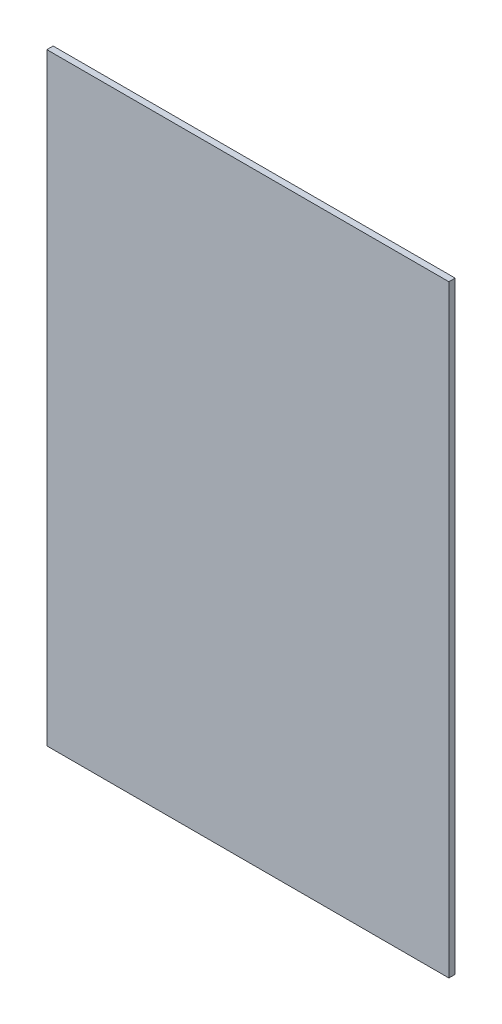
SolidWorks part; units mm, degrees
ref_plane "Front Plane" through (0, 0, 0) normal (0, 0, 1) x (1, 0, 0)
ref_plane "Top Plane" through (0, 0, 0) normal (0, 1, 0) x (1, 0, 0)
ref_plane "Right Plane" through (0, 0, 0) normal (1, 0, 0) x (0, 0, -1)
sketch "Sketch1" plane through (0, 0, 0) normal (0, 0, 1) x (1, 0, 0)
  line L0 (0, 0) -> (203.2, 0)
  line L1 (203.2, 0) -> (203.2, 304.8)
  line L2 (203.2, 304.8) -> (0, 304.8)
  line L3 (0, 304.8) -> (0, 0)
  dimension "D1" = 203.2
  dimension "D2" = 304.8
extrude "Boss-Extrude1" add sketch "Sketch1" along normal blind 3.175
equation "\"wall_thickness\" = 0.125in"
equation "\"base_thickness\" = 0.25in"
equation "\"D1@Boss-Extrude1\"=\"wall_thickness\""
